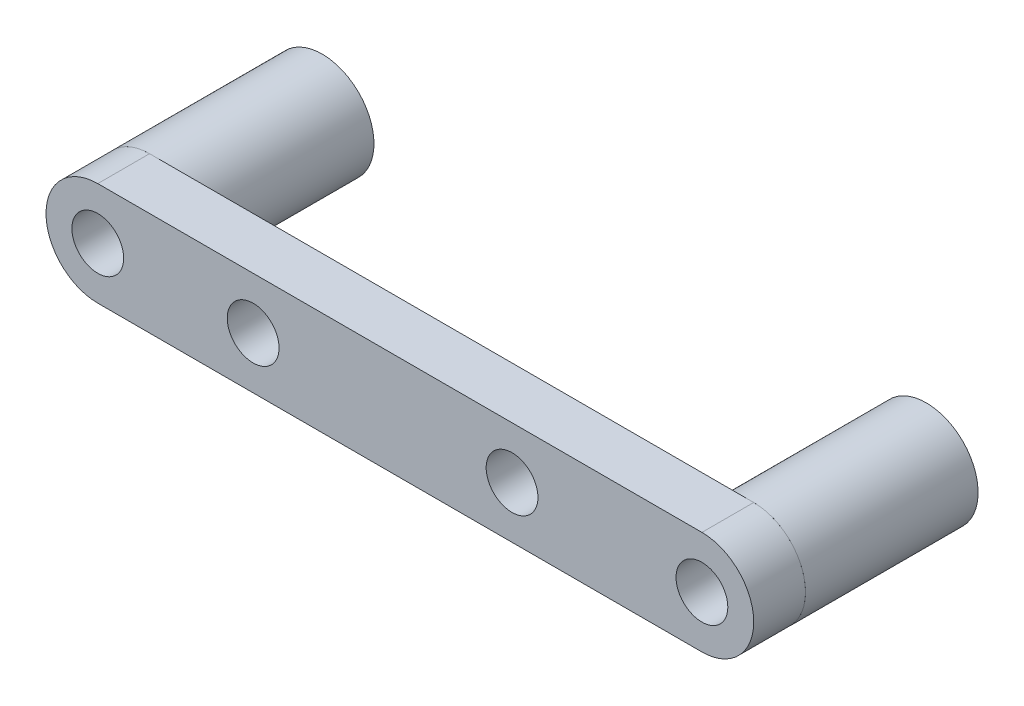
SolidWorks part; units mm, degrees
ref_plane "正面" through (0, 0, 0) normal (0, 0, 1) x (1, 0, 0)
ref_plane "平面" through (0, 0, 0) normal (0, 1, 0) x (1, 0, 0)
ref_plane "右側面" through (0, 0, 0) normal (1, 0, 0) x (0, 0, -1)
sketch "ｽｹｯﾁ1" plane through (0, 0, 0) normal (0, 0, 1) x (1, 0, 0)
  line L0 (-7.5, 0) -> (7.5, 0) construction
  line L1 (-7.5, 3) -> (7.5, 3)
  line L2 (-7.5, -3) -> (7.5, -3)
  arc A0 (-7.5, 3) -> (-7.5, -3) centre (-7.5, 0) ccw
  arc A1 (7.5, -3) -> (7.5, 3) centre (7.5, 0) ccw
  circle A2 centre (-7.5, 0) radius 1.5
  circle A3 centre (7.5, 0) radius 1.5
  point P2 (0, 0)
  dimension "D1" = 3
  dimension "D3" = 3
  dimension "D2" = 15
extrude "ﾎﾞｽ - 押し出し1" add sketch "ｽｹｯﾁ1" along normal blind 3
sketch "ｽｹｯﾁ2" plane through (0, 0, 3) normal (0, 0, 1) x (1, 0, 0)
  line L0 (-7.5, 3) -> (-16.5, 3)
  line L1 (-7.5, -3) -> (-16.5, -3)
  line L2 (7.5, 3) -> (18.5, 3)
  line L4 (7.5, -3) -> (18.5, -3)
  arc A0 (-16.5, 3) -> (-16.5, -3) centre (-16.5, 0) ccw
  arc A1 (-7.5, 3) -> (-7.5, -3) centre (-7.5, 0) ccw construction
  arc A2 (-7.5, 3) -> (-7.5, -3) centre (-7.5, 0) ccw
  circle A3 centre (-16.5, 0) radius 1.5
  arc A4 (7.5, -3) -> (7.5, 3) centre (7.5, 0) ccw construction
  arc A5 (7.5, -3) -> (7.5, 3) centre (7.5, 0) ccw
  arc A6 (18.5, 3) -> (18.5, -3) centre (18.5, 0) cw
  circle A7 centre (18.5, 0) radius 1.5
  circle A8 centre (7.5, 0) radius 1.5 construction
  dimension "D1" = 9
  dimension "D2" = 3
  dimension "D3" = 11
extrude "ﾎﾞｽ - 押し出し2" add sketch "ｽｹｯﾁ2" against normal up to surface (3 mm away) up to face at (0, 0, 0)
sketch "ｽｹｯﾁ3" plane through (0, 0, 0) normal (0, 0, -1) x (-1, 0, 0)
  circle A0 centre (16.5, 0) radius 1.5
  circle A1 centre (16.5, 0) radius 3
  circle A2 centre (-18.5, 0) radius 1.5 construction
  circle A3 centre (-18.5, 0) radius 1.5
  circle A4 centre (-18.5, 0) radius 3
  dimension "D1" = 3
  dimension "D2" = 6
extrude "ﾎﾞｽ - 押し出し3" add sketch "ｽｹｯﾁ3" along normal blind 10 separate body
